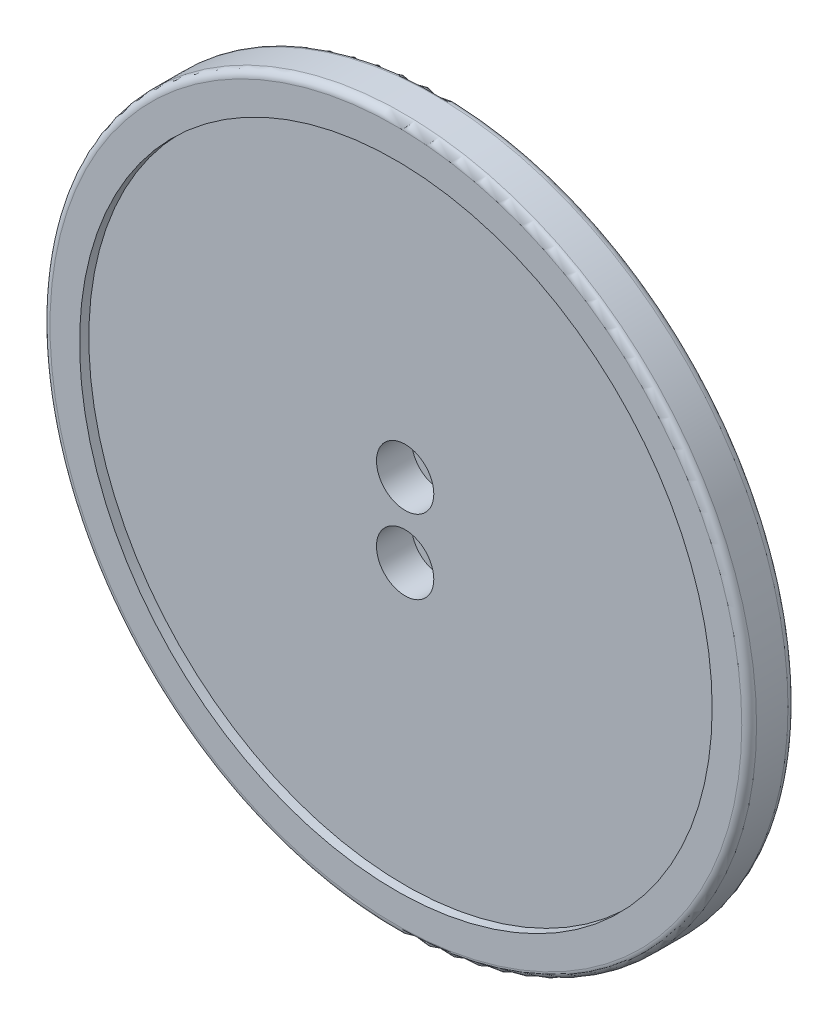
SolidWorks part; units mm, degrees
ref_plane "Front Plane" through (0, 0, 0) normal (1, 0, 0) x (0, 1, 0)
ref_plane "Top Plane" through (0, 0, 0) normal (0, 0, 1) x (0, 1, 0)
ref_plane "Right Plane" through (0, 0, 0) normal (0, 1, 0) x (-1, 0, 0)
sketch "Sketch1" plane through (0, 0, 0) normal (0, 0, 1) x (0, 1, 0)
  circle A0 centre (0, 0) radius 42.75
  circle A1 centre (0, 0) radius 47.75
  dimension "D1" = 85.5
  dimension "D2" = 5
extrude "Boss-Extrude1" add sketch "Sketch1" along normal blind 1.25
sketch "Sketch2" plane through (0, 0, 0) normal (0, 0, -1) x (1, 0, 0)
  line L0 (0, -5) -> (0, 5) construction
  circle A0 centre (0, 0) radius 47.75
  circle A1 centre (0, 5) radius 2.25
  circle A2 centre (0, -5) radius 2.25
  point P5 (0, 0)
  dimension "D1" = 4.5
  dimension "D2" = 10
extrude "Boss-Extrude2" add sketch "Sketch2" along normal blind 5
sketch "Sketch3" plane through (0, 0, 0) normal (0, 0, 1) x (1, 0, 0)
  circle A0 centre (0, 5) radius 3.875
  circle A1 centre (0, -5) radius 3.875
  dimension "D1" = 7.75
extrude "Cut-Extrude1" cut sketch "Sketch3" against normal blind 4.75
sketch "Sketch4" plane through (0, 0, -5) normal (0, 0, -1) x (1, 0, 0)
  line L1 (-6.35, -10) -> (6.35, -10)
  line L2 (-6.35, -10) -> (-6.35, 10)
  line L3 (-6.35, 10) -> (6.35, 10)
  line L4 (6.35, -10) -> (6.35, 10)
  line L5 (-6.35, -10) -> (6.35, 10) construction
  line L6 (-6.35, 10) -> (6.35, -10) construction
  circle A0 centre (0, -5) radius 2.25 construction
  point P0 (0, 0)
  circle M5 centre (0, 5) radius 2.25
  circle M7 centre (0, -5) radius 2.25
  dimension "D2" = 5
  dimension "D1" = 12.7
extrude "Boss-Extrude3" add sketch "Sketch4" along normal blind 10 contours L1 L4 L3 L2 M5 M7 region at (0, 0, -5)
fillet "Fillet1" radius 10 4 edges at (0, -10, -5) (-6.35, 0, -5) (0, 10, -5) (6.35, 0, -5)
fillet "Fillet2" radius 1 2 edges at (-47.75, 0, -5) (47.75, 0, 1.25)
